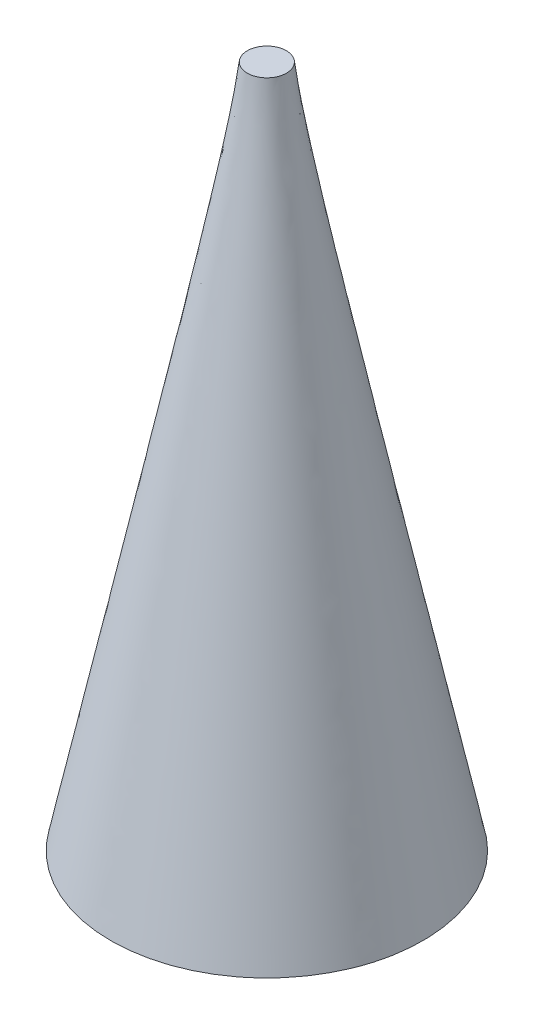
SolidWorks part; units mm, degrees
ref_plane "Front Plane" through (0, 0, 0) normal (0, 0, 1) x (1, 0, 0)
ref_plane "Top Plane" through (0, 0, 0) normal (0, 1, 0) x (1, 0, 0)
ref_plane "Right Plane" through (0, 0, 0) normal (1, 0, 0) x (0, 0, -1)
sketch "Sketch1" plane through (0, 0, 0) normal (0, 1, 0) x (1, 0, 0)
  circle A0 centre (0, 0) radius 40
  dimension "D1" = 80
ref_plane "Plane1" through (0, 100, 0) normal (0, 1, 0) x (1, 0, 0)
sketch "Sketch2" plane through (0, 100, 0) normal (0, 1, 0) x (1, 0, 0)
  circle A0 centre (0, 0) radius 5
  dimension "D1" = 10
ref_plane "Plane2" through (0, 175, 0) normal (0, 1, 0) x (1, 0, 0)
sketch "Sketch3" plane through (0, 175, 0) normal (0, 1, 0) x (1, 0, 0)
  circle A0 centre (0, 0) radius 5
  dimension "D1" = 10
loft "Loft2" add profiles "Sketch1", "Sketch3" connector at (-34.1187, 0, -20.8785) connector at (-4.763, 175, 1.5212)
